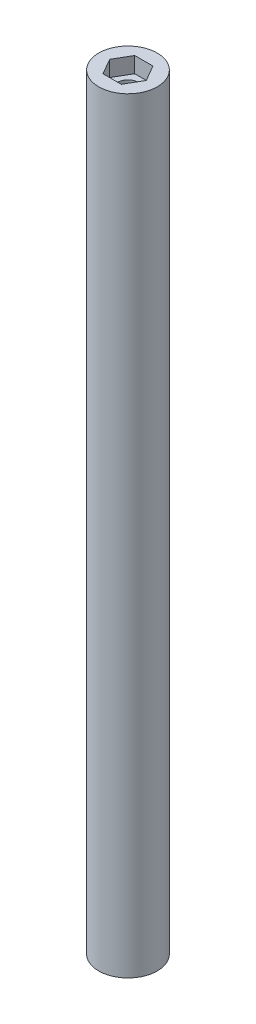
SolidWorks part; units mm, degrees
ref_plane "Front Plane" through (0, 0, 0) normal (0, 0, 1) x (1, 0, 0)
ref_plane "Top Plane" through (0, 0, 0) normal (0, 1, 0) x (1, 0, 0)
ref_plane "Right Plane" through (0, 0, 0) normal (1, 0, 0) x (0, 0, -1)
sketch "Sketch1" plane through (0, 0, 0) normal (0, 1, 0) x (1, 0, 0)
  circle A0 centre (0, 0) radius 5
  circle A1 centre (0, 0) radius 1.75
  dimension "D1" = 10
  dimension "D2" = 3.5
extrude "Boss-Extrude1" add sketch "Sketch1" along normal blind 130.8
sketch "Sketch2" plane through (0, 130.8, 0) normal (0, 1, 0) x (1, 0, 0)
  line L1 (3.125, 0) -> (1.5625, 2.7063)
  line L2 (1.5625, 2.7063) -> (-1.5625, 2.7063)
  line L3 (-1.5625, 2.7063) -> (-3.125, 0)
  line L4 (-3.125, 0) -> (-1.5625, -2.7063)
  line L5 (-1.5625, -2.7063) -> (1.5625, -2.7063)
  line L6 (1.5625, -2.7063) -> (3.125, 0)
  line L7 (0, 0) -> (50000, 0) construction
  circle A0 centre (0, 0) radius 2.7063 construction
  dimension "D1" = 6.25
extrude "Cut-Extrude1" cut sketch "Sketch2" against normal blind 2.7
sketch "Sketch3" plane through (0, 0, 0) normal (0, -1, 0) x (1, 0, 0)
  line L6 (7.1145, 0) -> (50007.1145, 0) construction
  line L8 (3.125, 0) -> (1.5625, 2.7063)
  line L9 (1.5625, 2.7063) -> (-1.5625, 2.7063)
  line L10 (-1.5625, 2.7063) -> (-3.125, 0)
  line L11 (-3.125, 0) -> (-1.5625, -2.7063)
  line L12 (-1.5625, -2.7063) -> (1.5625, -2.7063)
  line L13 (1.5625, -2.7063) -> (3.125, 0)
  circle A1 centre (0, 0) radius 2.7063 construction
  dimension "D1" = 6.25
extrude "Cut-Extrude2" cut sketch "Sketch3" against normal blind 2.7
